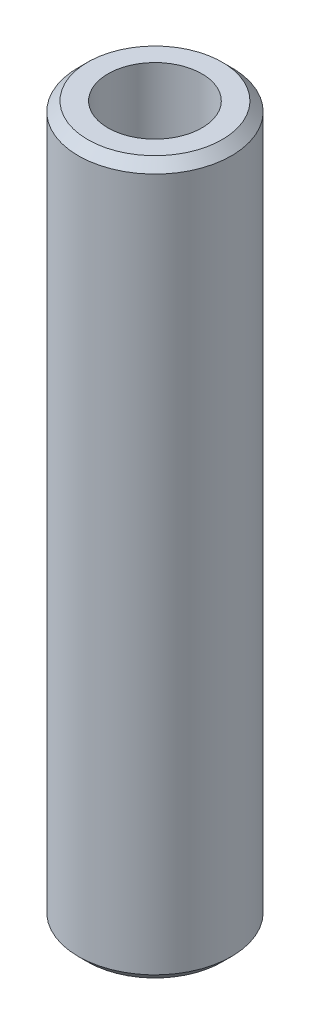
SolidWorks part; units mm, degrees
ref_plane "Front Plane" through (0, 0, 0) normal (0, 0, 1) x (1, 0, 0)
ref_plane "Top Plane" through (0, 0, 0) normal (0, 1, 0) x (1, 0, 0)
ref_plane "Right Plane" through (0, 0, 0) normal (1, 0, 0) x (0, 0, -1)
sketch "Sketch1" plane through (0, 0, 0) normal (0, 1, 0) x (1, 0, 0)
  circle A0 centre (0, 0) radius 15
  dimension "SHAFT_OD" = 30
extrude "Boss-Extrude1" add sketch "Sketch1" along normal blind 139.5751
sketch "Sketch2" plane through (0, 0, 0) normal (0, 1, 0) x (1, 0, 0)
  circle A0 centre (0, 0) radius 9.2007
  dimension "BORE_D" = 18.4015
extrude "Cut-Extrude1" cut sketch "Sketch2" along normal through all
chamfer "Chamfer1" distance 1.8318 angle 45 2 edges at (0, 139.5751, 15) (0, 0, 15)
